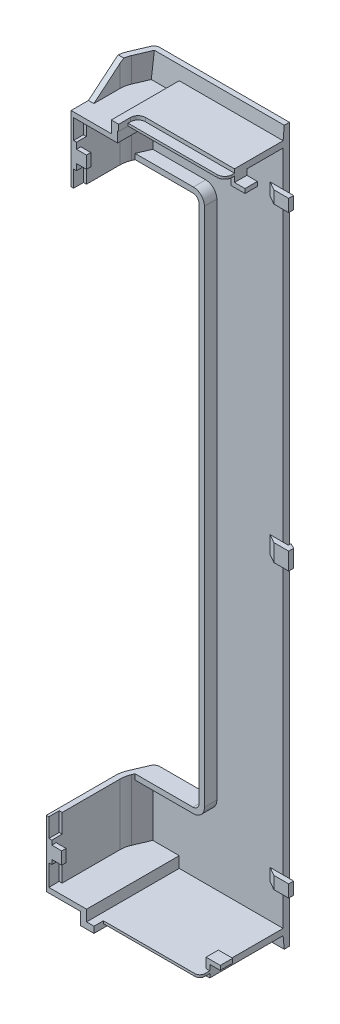
SolidWorks part; units mm, degrees
note: The reader was unsure of these and kept them because the rebuilt part matched: shared geometry of "Sketch4<3>", "Sketch2<3>", "Sketch2<4>", "Sketch7<3>", "Sketch8<3>".
ref_plane "Front Plane" through (0, 0, 0) normal (1, 0, 0) x (0, 1, 0)
ref_plane "Top Plane" through (0, 0, 0) normal (0, 0, 1) x (0, 1, 0)
ref_plane "Right Plane" through (0, 0, 0) normal (0, 1, 0) x (-1, 0, 0)
sketch "Sketch1" plane through (0, 0, 0) normal (0, 0, 1) x (0, 1, 0)
  line L0 (-107.5, 27) -> (-144.25, 27)
  line L2 (-144.25, 27) -> (-144.25, -27)
  line L3 (-144.25, -27) -> (144.25, -27)
  line L4 (144.25, 27) -> (144.25, -27)
  line L5 (-144.25, 27) -> (144.25, -27) construction
  line L6 (-144.25, -27) -> (144.25, 27) construction
  line L8 (107.5, 27) -> (107.5, 2)
  line L9 (107.5, 2) -> (-107.5, 2)
  line L10 (-107.5, 27) -> (-107.5, 2)
  line L11 (107.5, 27) -> (144.25, 27)
  point P0 (0, 0)
  dimension "D1" = 288.5
  dimension "D2" = 54
  dimension "D3" = 25
  dimension "D4" = 215
extrude "Boss-Extrude1" add sketch "Sketch1" along normal blind 2.54
sketch "Sketch4" plane through (0, -144.25, 0) normal (0, -1, 0) x (1, 0, 0)
  line L0 (-27, 0) -> (-30.4469, 8.0735)
  line L1 (-31.25, 12) -> (-31.25, 40)
  line L2 (27, 2.54) -> (27, 0) construction
  line L3 (-27, 0) -> (27, 0) construction
  line L4 (-31.25, 40) -> (-29.05, 40)
  line L5 (-29.05, 40) -> (-29.05, 12.45)
  line L6 (-28.2469, 8.5235) -> (-25.6923, 2.54)
  line L10 (-25.6923, 2.54) -> (-27.7156, 1.6762) construction
  line L11 (-25.6923, 2.54) -> (-27, 2.54)
  line L12 (-27, 2.54) -> (-27, 0)
  line L13 (-29.05, 30) -> (-31.25, 30)
  arc A0 (-30.4469, 8.0735) -> (-31.25, 12) centre (-21.25, 12) cw
  arc A1 (-29.05, 12.45) -> (-28.2469, 8.5235) centre (-19.05, 12.45) ccw
  line M14 (27, 2.54) -> (-27, 2.54)
  line M15 (-27, 2.54) -> (-27, 0)
  dimension "D1" = 10
  dimension "D5" = 10
  dimension "D2" = 58.25
  dimension "D3" = 40
  dimension "D4" = 12
  dimension "D6" = 2.54
  dimension "D7" = 2.2
  dimension "D8" = 30
  dimension "D9" = 2.2
extrude "Boss-Extrude2" add sketch "Sketch4" along normal up to surface (36.75 mm away) from surface at -288.5 contours L10 L6 A1 L5 L13 L1 A0 L0 M15 M14 | L12 L10 L0 up to face at (-14.5, 107.5, 1.27) starting at face at (0, 144.25, 1.27)
extrude "Boss-Extrude3" add sketch "Sketch4<3>" along normal through all from surface contours L10 L6 A1 L5 L13 L1 A0 L0 M15 M14 | L13 L5 L4 L1 | L12 L10 L0
sketch "Sketch4<3>" plane through (0, -144.25, 0) normal (0, -1, 0) x (1, 0, 0) same geometry as "Sketch4"
sketch "Sketch5" plane through (-31.25, 0, 0) normal (-1, 0, 0) x (0, -1, 0)
  line L0 (-134.25, 30) -> (-134.25, 23)
  line L1 (-107.5, 30) -> (-144.25, 30) construction
  line L2 (-134.25, 23) -> (-144.25, 11)
  line L3 (-144.25, 11) -> (-144.25, 30)
  line L4 (-144.25, 30) -> (-134.25, 30)
  line L5 (144.25, 12) -> (144.25, 40) construction
  line L6 (144.25, 11) -> (134.25, 23)
  line L7 (-144.25, 0) -> (-107.5, 0) construction
  line L8 (144.25, 40) -> (134.25, 40)
  line L9 (144.25, 40) -> (107.5, 40) construction
  line L10 (134.25, 40) -> (134.25, 23)
  line L11 (144.25, 0) -> (144.25, 8.0735) construction
  line L12 (144.25, 11) -> (144.25, 40)
  dimension "D1" = 11
  dimension "D2" = 10
  dimension "D3" = 7
extrude "Cut-Extrude1" cut sketch "Sketch5" against normal through all
sketch "Sketch2" plane through (0, 0, 2.54) normal (0, 0, 1) x (1, 0, 0)
  line L1 (27, 144.25) -> (-25.6923, 144.25) construction
  line L2 (-29.05, 134.25) -> (-15, 134.25)
  line L4 (-15, 134.25) -> (-15, 139.05)
  line L5 (-15, 139.05) -> (27, 139.05)
  line L6 (27, -144.25) -> (27, 144.25) construction
  line L7 (27, 139.05) -> (27, 136.51)
  line L8 (27, 136.51) -> (-12.46, 136.51)
  line L9 (-12.46, 136.51) -> (-12.46, 132.25)
  line L10 (-12.46, 132.25) -> (-29.05, 132.25)
  line L16 (-29.05, -132.25) -> (-15, -132.25)
  line L17 (-15, -132.25) -> (-15, -136.71)
  line L18 (-15, -136.71) -> (27, -136.71)
  line L19 (27, -136.71) -> (27, -139.25)
  line L20 (27, -139.25) -> (-17.54, -139.25)
  line L21 (-17.54, -139.25) -> (-17.54, -134.25)
  line L22 (-17.54, -134.25) -> (-29.05, -134.25)
  line L24 (-25.6923, -144.25) -> (27, -144.25) construction
  line L32 (-15, 134.25) -> (-12.46, 134.25) construction
  line L33 (-2, 109.7) -> (-2, 107.5) construction
  line L34 (0.2, 107.5) -> (-2, 107.5) construction
  line L35 (-2, -109.7) -> (-2, -107.5) construction
  line L36 (-17.54, -134.25) -> (-15, -134.25) construction
  line L37 (-17.54, -134.25) -> (-17.54, -132.25) construction
  line L38 (-15, 134.25) -> (-15, 132.25) construction
  line L39 (-29.05, -134.25) -> (-29.05, -132.25)
  line L42 (-29.05, 107.5) -> (-29.05, 109.7)
  line L43 (-31.25, 107.5) -> (-29.05, 107.5) construction
  line L44 (-25.6923, 107.5) -> (-2, 107.5) construction
  line L45 (-29.05, 109.7) -> (0.2, 109.7)
  line L46 (-29.05, 132.25) -> (-29.05, 134.25)
  line L47 (0.2, 109.7) -> (0.2, -109.7)
  line L48 (0.2, -109.7) -> (-29.05, -109.7)
  line L50 (-29.05, -109.7) -> (-29.05, -107.5)
  line L54 (-29.05, -107.5) -> (-2, -107.5)
  line L55 (-2, -107.5) -> (-2, 107.5)
  line L56 (-2, 107.5) -> (-29.05, 107.5)
  line L61 (-29.05, -143.0417) -> (-29.05, -107.5) construction
  line L62 (-29.05, 107.5) -> (-29.05, 143.0417) construction
  line M38 (-25.6923, 107.5) -> (-2, 107.5)
  line M39 (-2, 107.5) -> (-2, -107.5)
  line M40 (-2, -107.5) -> (-25.6923, -107.5)
  line M43 (27, -144.25) -> (27, 144.25)
  line M44 (-25.6923, -107.5) -> (-25.6923, -144.25)
  line M45 (-25.6923, 144.25) -> (-25.6923, 107.5)
  dimension "D1" = 2.54
  dimension "D2" = 2.54
  dimension "D3" = 5.2
  dimension "D4" = 5
  dimension "D5" = 14.05
  dimension "D6" = 42
  dimension "D7" = 4.26
  dimension "D8" = 2
  dimension "D9" = 2
extrude "Boss-Extrude4" add sketch "Sketch2" along normal blind 5 contours L48 L47 L45 M45 M38 M39 M40 M44 | L54 L50 L48 M44 | L56 L45 L42 M45
fillet "Fillet1" radius 4.5 2 edges at (0.2, -109.7, 5.04) (0.2, 109.7, 5.04)
fillet "Fillet2" radius 2.5 2 edges at (-2, -107.5, 3.77) (-2, 107.5, 3.77)
extrude "Boss-Extrude5" add sketch "Sketch2<3>" along normal up to surface (37.46 mm away) contours L22 L21 L20 L18 L17 L16 M43 M44 | L39 L22 L16 M44 up to face at (-30.15, -120.875, 40)
sketch "Sketch2<3>" plane through (0, 0, 2.54) normal (0, 0, 1) x (1, 0, 0) same geometry as "Sketch2"
extrude "Boss-Extrude6" add sketch "Sketch2<4>" along normal up to surface (27.46 mm away) contours L46 L10 L2 M45 | L10 L9 L8 L5 L4 L2 M43 M45 up to face at (-30.15, 120.875, 30)
sketch "Sketch2<4>" plane through (0, 0, 2.54) normal (0, 0, 1) x (1, 0, 0) same geometry as "Sketch2"
sketch "Sketch11" plane through (0, -144.25, 0) normal (0, -1, 0) x (1, 0, 0)
  line L0 (-27, 0) -> (-30.4469, 8.0735)
  line L1 (-30.4469, 8.0735) -> (-30.4469, 0)
  line L2 (-30.4469, 0) -> (-27, 0)
extrude "Cut-Extrude8" cut sketch "Sketch11" against normal through all
fillet "Fillet3" radius 2.5 2 edges at (-27, 125.875, 0) (-27, -125.875, 0)
sketch "Sketch7" plane through (0, -139.25, 0) normal (0, -1, 0) x (1, 0, 0)
  line L0 (27, 32.2) -> (-10, 32.2)
  line L1 (27, 40) -> (27, 2.54) construction
  line L2 (-12, 34.2) -> (-12, 40)
  line L3 (27, 40) -> (-17.54, 40) construction
  line L4 (-12, 40) -> (27, 40)
  line L5 (27, 40) -> (27, 32.2)
  line L6 (27, 32.2) -> (27, 34.2)
  line L7 (25, 36.2) -> (-12, 36.2)
  line L8 (27, 32.2) -> (27, 36.2)
  arc A0 (-10, 32.2) -> (-12, 34.2) centre (-10, 34.2) cw
  arc A1 (27, 34.2) -> (25, 36.2) centre (25, 34.2) ccw
  line M7 (27, 2.54) -> (27, 40)
  line M8 (27, 40) -> (-17.54, 40)
  dimension "D1" = 2
  dimension "D2" = 2
  dimension "D4" = 39
  dimension "D3" = 7.8
  dimension "D5" = 4
extrude "Cut-Extrude2" cut sketch "Sketch7" against normal up to surface (2.54 mm away) contours A1 L5 L2 L7 M7 M8 up to face at (6, -136.71, 21.27)
extrude "Cut-Extrude3" cut sketch "Sketch7<3>" against normal offset from surface (1.54 mm away) 1 contours A1 L7 L2 A0 L0 M7 up to face at (3.6306, -136.71, 27.442)
sketch "Sketch7<3>" plane through (0, -139.25, 0) normal (0, -1, 0) x (1, 0, 0) same geometry as "Sketch7"
sketch "Sketch8" plane through (0, 139.05, 0) normal (0, 1, 0) x (-1, 0, 0)
  line L0 (12, 30) -> (12, 25.2)
  line L1 (-27, 30) -> (15, 30) construction
  line L2 (9, 22.2) -> (-27, 22.2)
  line L3 (-27, 30) -> (-27, 2.54) construction
  line L4 (12, 26.2) -> (-24, 26.2)
  line L5 (-27, 23.2) -> (-27, 22.2)
  line L6 (12, 30) -> (-27, 30)
  line L7 (-27, 30) -> (-27, 22.2)
  line L9 (-27, 22.2) -> (-27, 30) construction
  arc A0 (12, 25.2) -> (9, 22.2) centre (9, 25.2) cw
  arc A1 (-24, 26.2) -> (-27, 23.2) centre (-24, 23.2) ccw
  point P15 (-27, 26.25)
  point P21 (-27, 26.1)
  line M8 (15, 30) -> (-27, 30)
  line M9 (-27, 30) -> (-27, 2.54)
  dimension "D1" = 3
  dimension "D2" = 3
  dimension "D3" = 7.8
  dimension "D4" = 39
  dimension "D5" = 4
extrude "Cut-Extrude4" cut sketch "Sketch8" against normal up to surface (2.54 mm away) contours A1 L4 L0 M8 M9 up to face at (7.27, 136.51, 16.27)
extrude "Cut-Extrude5" cut sketch "Sketch8<3>" against normal offset from surface (1.54 mm away) 1 contours L4 A1 L2 A0 L0 M9 up to face at (4.243, 136.51, 20.1859)
sketch "Sketch8<3>" plane through (0, 139.05, 0) normal (0, 1, 0) x (-1, 0, 0) same geometry as "Sketch8"
sketch "Sketch9" plane through (-29.05, 0, 0) normal (1, 0, 0) x (0, 1, 0)
  line L1 (-132.25, 40) -> (-123.65, 40)
  line L2 (-132.25, 40) -> (-132.25, 35.8)
  line L3 (-132.25, 35.8) -> (-123.65, 35.8)
  line L4 (-123.65, 40) -> (-123.65, 35.8)
  line L5 (-107.5, 40) -> (-115.1, 40)
  line L6 (-107.5, 40) -> (-107.5, 35.8)
  line L7 (-107.5, 35.8) -> (-115.1, 35.8)
  line L8 (-115.1, 40) -> (-115.1, 35.8)
  dimension "D1" = 7.6
  dimension "D2" = 8.55
  dimension "D3" = 8.6
  dimension "D4" = 4.2
extrude "Cut-Extrude6" cut sketch "Sketch9" against normal offset from surface (1.2 mm away) 1 up to face at (-31.25, -125.3833, 25.4)
sketch "Sketch10" plane through (-29.05, 0, 0) normal (1, 0, 0) x (0, 1, 0)
  line L1 (107.5, 30) -> (114.25, 30)
  line L2 (107.5, 30) -> (107.5, 26)
  line L3 (107.5, 26) -> (114.25, 26)
  line L4 (114.25, 30) -> (114.25, 26)
  line L5 (132.25, 30) -> (124.25, 30)
  line L6 (132.25, 30) -> (132.25, 26)
  line L7 (132.25, 26) -> (124.25, 26)
  line L8 (124.25, 30) -> (124.25, 26)
  dimension "D1" = 4
  dimension "D3" = 10
  dimension "D4" = 8
extrude "Cut-Extrude7" cut sketch "Sketch10" against normal offset from surface (1.2 mm away) 1 up to face at (-31.25, 125.3833, 21.4)
sketch "Sketch12" plane through (0, 0, 2.54) normal (0, 0, 1) x (1, 0, 0)
  line L0 (27, 144.25) -> (27, -144.25) construction
  line L1 (25.25, -118) -> (31.25, -118)
  line L2 (25.25, -118) -> (25.25, -123)
  line L3 (25.25, -123) -> (31.25, -123)
  line L4 (31.25, -118) -> (31.25, -123)
  line L5 (25.25, -1.5) -> (31.25, -1.5)
  line L6 (25.25, -1.5) -> (25.25, -8.5)
  line L7 (25.25, -8.5) -> (31.25, -8.5)
  line L8 (31.25, -1.5) -> (31.25, -8.5)
  line L9 (25.25, 122) -> (31.25, 122)
  line L10 (25.25, 122) -> (25.25, 117)
  line L11 (25.25, 117) -> (31.25, 117)
  line L12 (31.25, 122) -> (31.25, 117)
  line L14 (31.25, 119.5) -> (25.25, 119.5) construction
  line L15 (31.25, -5) -> (25.25, -5) construction
  line L16 (31.25, -120.5) -> (25.25, -120.5) construction
  line L17 (27, 0) -> (0, 0) construction
  line L18 (27, -136.71) -> (27, 136.51) construction
  dimension "D1" = 5
  dimension "D2" = 7
  dimension "D3" = 115.5
  dimension "D4" = 124.5
  dimension "D5" = 5
  dimension "D6" = 4.25
  dimension "D7" = 6
  dimension "D8" = 27
extrude "Boss-Extrude7" add sketch "Sketch12" along normal blind 2
draft "Draft1" type of draft neutral plane draft angle 60 faces to draft 3 face at (25.25, -120.5, 3.54) face at (25.25, -5, 3.54) face at (25.25, 119.5, 3.54) neutral plane through (0, 0, 4.54) neutral plane normal (0, 0, 1) parameters "D1"=60
sketch "Sketch13" plane through (-29.05, 0, 0) normal (1, 0, 0) x (0, 1, 0)
  line L0 (-123.65, 40) -> (-115.1, 40) construction
  line L1 (-121.875, 40) -> (-116.875, 40)
  line L2 (-121.875, 40) -> (-121.875, 38.25)
  line L3 (-121.875, 38.25) -> (-116.875, 38.25)
  line L4 (-116.875, 40) -> (-116.875, 38.25)
  line L5 (114.25, 30) -> (124.25, 30) construction
  line L6 (116.75, 30) -> (121.75, 30)
  line L7 (116.75, 30) -> (116.75, 28.25)
  line L8 (116.75, 28.25) -> (121.75, 28.25)
  line L9 (121.75, 30) -> (121.75, 28.25)
  point P13 (119.25, 30)
  point P14 (-119.375, 40)
  dimension "D1" = 5
  dimension "D2" = 1.75
extrude "Boss-Extrude8" add sketch "Sketch13" along normal blind 4
ref_plane "Plane1" through (25.5, 0, 0) normal (1, 0, 0) x (0, 1, 0)
sketch "Sketch14" plane through (25.5, 0, 0) normal (1, 0, 0) x (0, 1, 0)
  line L0 (136.51, 23.2) -> (136.51, 2.54) construction
  line L1 (136.51, 22.2) -> (132.51, 22.2)
  line L2 (136.51, 22.2) -> (136.51, 17.2)
  line L3 (136.51, 17.2) -> (132.51, 17.2)
  line L4 (132.51, 22.2) -> (132.51, 17.2)
  line L5 (-136.71, 34.2) -> (-136.71, 2.54) construction
  line L6 (-136.71, 32.2) -> (-132.71, 32.2)
  line L7 (-136.71, 32.2) -> (-136.71, 27.2)
  line L8 (-136.71, 27.2) -> (-132.71, 27.2)
  line L9 (-132.71, 32.2) -> (-132.71, 27.2)
  line L10 (136.51, 26.2) -> (137.51, 26.2) construction
  line L11 (-136.71, 36.2) -> (-137.71, 36.2) construction
  dimension "D1" = 5
  dimension "D2" = 4
  dimension "D3" = 4
  dimension "D4" = 4
extrude "Boss-Extrude9" add sketch "Sketch14" along normal blind 1.5
sketch "Sketch15" plane through (27, 0, 0) normal (1, 0, 0) x (0, 1, 0)
  line L0 (-136.71, 27.2) -> (-132.71, 27.2) construction
  line L1 (-132.71, 32.2) -> (-134.46, 32.2)
  line L2 (-132.71, 32.2) -> (-132.71, 27.2)
  line L3 (-132.71, 27.2) -> (-134.46, 27.2)
  line L4 (-134.46, 32.2) -> (-134.46, 27.2)
  line L5 (136.51, 22.2) -> (132.51, 22.2) construction
  line L6 (132.51, 17.2) -> (134.26, 17.2)
  line L7 (132.51, 17.2) -> (132.51, 22.2)
  line L8 (132.51, 22.2) -> (134.26, 22.2)
  line L9 (134.26, 17.2) -> (134.26, 22.2)
  dimension "D1" = 1.75
extrude "Boss-Extrude10" add sketch "Sketch15" along normal up to surface (4.25 mm away) up to face at (31.25, -120.5, 3.54)
draft "Draft2" type of draft neutral plane draft angle 5 faces to draft 1 face at (-4.5641, 139.1833, 2.54) neutral plane through (0, 139.05, 86.461) neutral plane normal (0, 1, 0) parameters "D1"=5
draft "Draft3" type of draft neutral plane draft angle 5 faces to draft 1 face at (-5.4108, -139.25, 2.54) neutral plane through (0, -139.25, 96.4854) neutral plane normal (0, -1, 0) parameters "D1"=5
sketch "Sketch16" plane through (0, 0, 2.54) normal (0, 0, -1) x (1, 0, 0)
  line L0 (31.25, 1.5) -> (27, 1.5) construction
  line L1 (31.25, 8.5) -> (29.125, 8.5)
  line L2 (31.25, 8.5) -> (31.25, 1.5)
  line L3 (31.25, 1.5) -> (29.125, 1.5)
  line L4 (29.125, 8.5) -> (29.125, 1.5)
  line L5 (27, 8.5) -> (31.25, 8.5) construction
  point P9 (29.125, 8.5)
extrude "Boss-Extrude11" add sketch "Sketch16" along normal blind 1
chamfer "Chamfer1" distance 1 distance2 2 1 edges at (31.25, -5, 1.54)
sketch "Sketch17" plane through (0, 0, 0) normal (0, 0, -1) x (1, 0, 0)
  line L0 (27, 0) -> (18, 0) construction
  line L1 (27, 144.25) -> (27, -144.25) construction
  line L2 (18, 0) -> (19.8, -5)
  line L3 (19.8, -5) -> (19.8, 5)
  line L4 (19.8, 5) -> (18, 0)
  line L5 (19.8, 5) -> (21, 5) construction
  line L6 (21, 5) -> (21.5, 5)
  line L7 (21, 5) -> (21, -5)
  line L8 (21, -5) -> (21.5, -5)
  line L9 (21.5, 5) -> (21.5, -5)
  line L10 (22.5, 5) -> (23, 5)
  line L11 (22.5, 5) -> (22.5, -5)
  line L12 (22.5, -5) -> (23, -5)
  line L13 (23, 5) -> (23, -5)
  line L14 (21.5, 5) -> (22.5, 5) construction
  point P15 (19.8, 0)
  point P16 (16.3212, 0)
  point P17 (19.1985, 0)
  point P18 (18.1897, 0)
  dimension "D1" = 1
  dimension "D2" = 1.2
  dimension "D3" = 0.5
  dimension "D4" = 1.8
  dimension "D5" = 10
  dimension "D6" = 4
extrude "Cut-Extrude9" cut sketch "Sketch17" against normal blind 1
